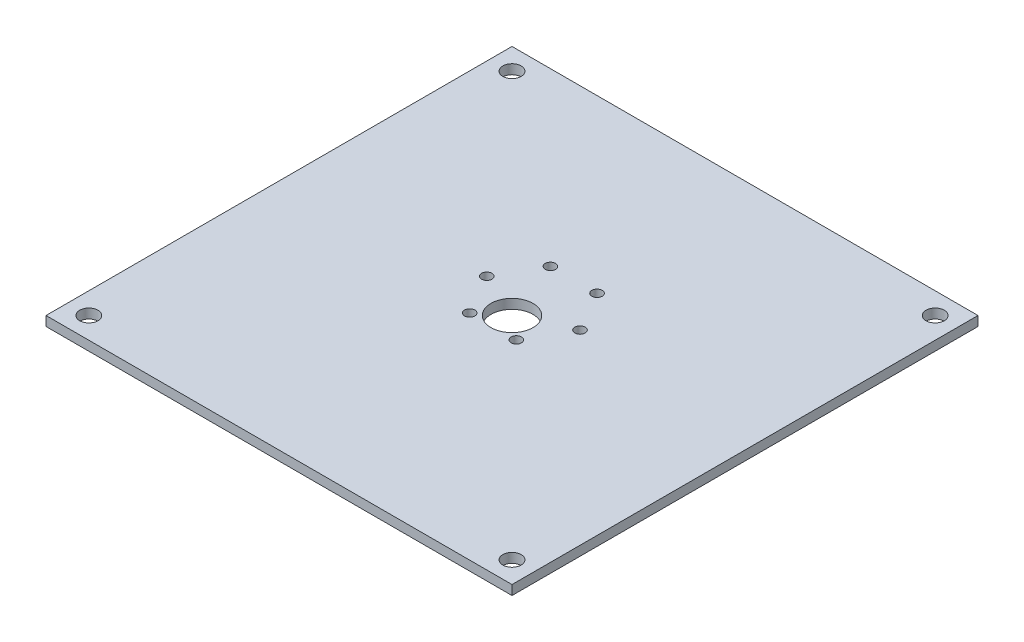
SolidWorks part; units mm, degrees
ref_plane "Front Plane" through (0, 0, 0) normal (0, 0, 1) x (1, 0, 0)
ref_plane "Top Plane" through (0, 0, 0) normal (0, 1, 0) x (1, 0, 0)
ref_plane "Right Plane" through (0, 0, 0) normal (1, 0, 0) x (0, 0, -1)
sketch "Sketch1" plane through (0, 0, 0) normal (0, 1, 0) x (1, 0, 0)
  line L1 (-77.47, -77.47) -> (77.47, -77.47)
  line L2 (-77.47, -77.47) -> (-77.47, 77.47)
  line L3 (-77.47, 77.47) -> (77.47, 77.47)
  line L4 (77.47, -77.47) -> (77.47, 77.47)
  line L5 (-77.47, -77.47) -> (77.47, 77.47) construction
  line L6 (-77.47, 77.47) -> (77.47, -77.47) construction
  circle A0 centre (0, 0) radius 6.985
  circle A1 centre (0, 7.112) radius 15.494 construction
  circle A2 centre (-15.494, 7.112) radius 1.72
  circle A3 centre (-7.747, 20.5302) radius 1.72
  circle A4 centre (7.747, 20.5302) radius 1.72
  circle A5 centre (15.494, 7.112) radius 1.72
  circle A6 centre (7.747, -6.3062) radius 1.72
  circle A7 centre (-7.747, -6.3062) radius 1.72
  circle A8 centre (-70.3501, -70.3501) radius 3.04 construction
  circle A9 centre (-70.3501, -70.3501) radius 3.04
  circle A10 centre (70.3501, -70.3501) radius 3.04 construction
  circle A11 centre (70.3501, 70.3501) radius 3.04 construction
  circle A12 centre (-70.3501, 70.3501) radius 3.04 construction
  circle A13 centre (70.3501, -70.3501) radius 3.04
  circle A14 centre (70.3501, 70.3501) radius 3.04
  circle A15 centre (-70.3501, 70.3501) radius 3.04
  point P0 (-6.3605, -8.3919)
  point P34 (0, 0)
  dimension "D4" = 13.97
  dimension "D6" = 3.44
  dimension "D1" = 154.94
  dimension "D2" = 154.94
  dimension "D3" = 7.112
  dimension "D7" = 30.988
  dimension "D5" = 6
extrude "Boss-Extrude1" add sketch "Sketch1" along normal mid plane 3.175 contours L1 L4 L3 L2 A7 A6 A5 A4 A3 A2 A0 region at (-75.2788, 0, 0)
